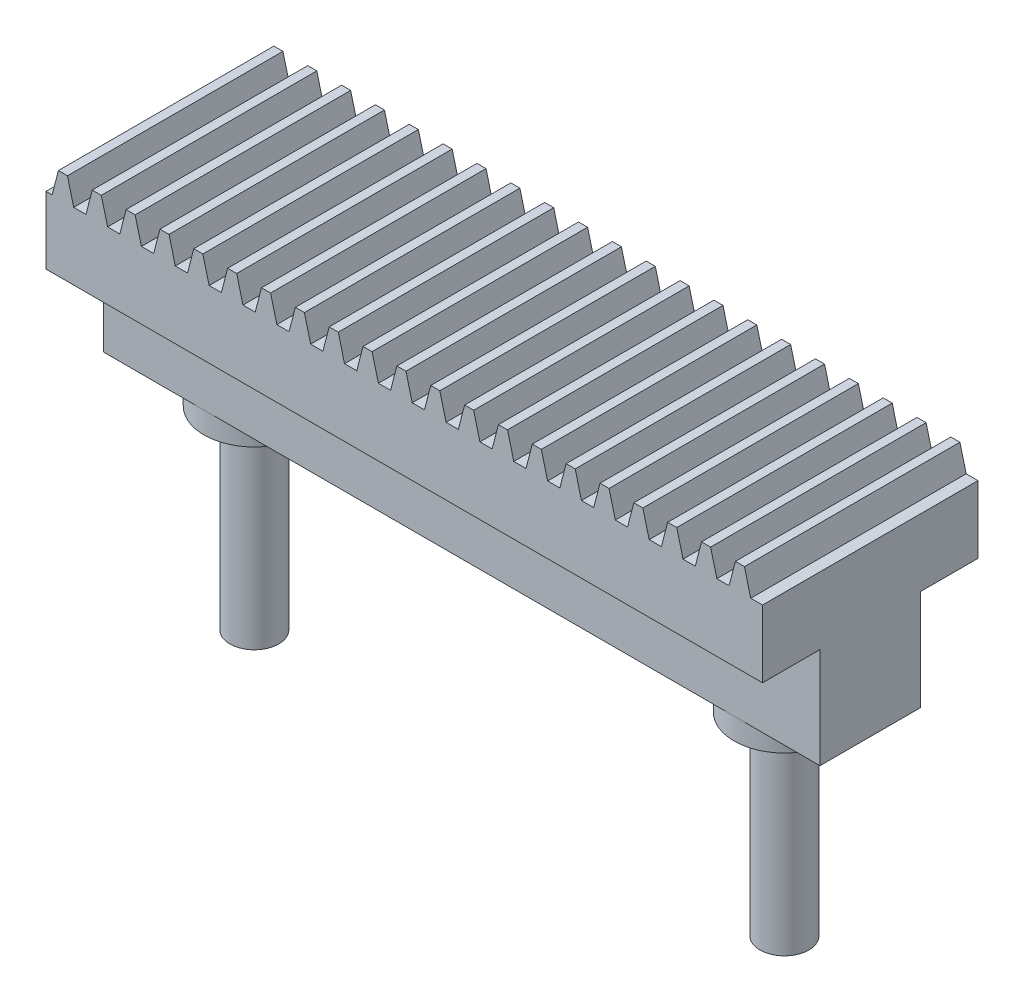
SolidWorks part; units mm, degrees
extrude "Blank" add sketch "BlankSke" against normal blind 20
sketch "BlankSke" plane through (0, 0, 0) normal (0, 0, 1) x (1, 0, 0)
  line L1 (0, 0) -> (100, 0)
  line L2 (0, 0) -> (0, 12.75)
  line L3 (0, 12.75) -> (100, 12.75)
  line L4 (100, 0) -> (100, 12.75)
  dimension "Length" = 100
ref_plane "Plane1" through (0, 0, 0) normal (0, 0, 1) x (1, 0, 0)
ref_plane "Plane2" through (0, 0, 0) normal (0, 1, 0) x (1, 0, 0)
ref_plane "Plane3" through (0, 0, 0) normal (1, 0, 0) x (0, 0, -1)
other "Configuration Table"
sketch "HoldingSke" plane through (0, 0, 0) normal (0, 1, 0) x (1, 0, 0)
  line L0 (0, 0) -> (0.0928, 0.6602)
  line L1 (-15, 0) -> (100, 0) construction
  line L2 (0, 0) -> (-2.1039, 2.3779)
  line L3 (0, 0) -> (-11.863, 4.5341)
  line L4 (0, 0) -> (7.9495, 3.3743)
  line L5 (0, 0) -> (-23.7986, -8.8762)
  line L6 (0, 0) -> (-10.5278, -7.1032)
  line L9 (-67.7845, 28.3722) -> (29.0302, 53.4102)
  line L10 (-76.2, 3.8779) -> (-64.95, 3.8779)
  line L11 (0, 0) -> (-20, 0)
  line L12 (-76.2, 101.6) -> (-76.147, 101.6)
  line L13 (24.9733, 27.94) -> (52.9518, 28.4284)
  line L14 (24.9733, 27.94) -> (24.9743, 27.94)
  line L15 (24.9733, 27.94) -> (100.4006, 29.5858)
  circle A0 centre (0, 0) radius 19.05
  circle A1 centre (0, 0) radius 5.625
  circle A2 centre (0, 0) radius 12.7
  dimension "Num_teeth" = 23
  dimension "Width" = 20
  dimension "Length" = 100
  dimension "Pitch_height" = 11.25
sketch "TooCutSkeIll" plane through (0, 0, 0) normal (0, 0, 1) x (1, 0, 0)
  line L0 (-1.7134, 12.705) -> (-0.9251, 9.6569)
  line L1 (-0.5611, 9.375) -> (0.5611, 9.375)
  line L2 (0.9251, 9.6569) -> (1.7134, 12.705)
  line L3 (100, 12.75) -> (0, 12.75) construction
  line L4 (0, 0) -> (0, 64.897) construction
  line L5 (-13.208, 11.25) -> (12.954, 11.25) construction
  line L6 (0, 0) -> (100, 0) construction
  line L7 (1.3371, 11.25) -> (1.3371, 48.7463) construction
  line L8 (-1.3371, 11.25) -> (-1.3371, 48.7463) construction
  line L9 (1.7715, 12.75) -> (1.7715, 12.7754)
  line L10 (-1.7715, 12.75) -> (-1.7715, 12.7754)
  line L11 (-1.7715, 12.7754) -> (1.7715, 12.7754)
  arc A0 (0.5611, 9.375) -> (0.9251, 9.6569) centre (0.5611, 9.751) ccw
  arc A1 (-0.9251, 9.6569) -> (-0.5611, 9.375) centre (-0.5611, 9.751) ccw
  arc A2 (1.7715, 12.75) -> (1.7134, 12.705) centre (1.7715, 12.69) ccw
  arc A3 (-1.7134, 12.705) -> (-1.7715, 12.75) centre (-1.7715, 12.69) ccw
  dimension "Addendum_plus" = 1.5254
  dimension "Pitch_height" = 11.25
  dimension "Pressure_angle" = 14.5
  dimension "Gap_width" = 2.6742
  dimension "Dedendum" = 1.875
extrude "ToothCutIll" [suppressed] cut sketch "TooCutSkeIll" against normal through all
sketch "TooCutSkeSim" plane through (0, 0, 0) normal (0, 0, 1) x (1, 0, 0)
  line L0 (0.8522, 9.375) -> (-0.8522, 9.375)
  line L1 (1.7316, 12.7754) -> (0.8522, 9.375)
  line L2 (0, 17.4625) -> (0, 53.467) construction
  line L3 (1.7316, 12.7754) -> (-1.7316, 12.7754)
  line L6 (-1.7316, 12.7754) -> (-0.8522, 9.375)
  line L9 (-1.3371, 11.25) -> (1.3371, 11.25) construction
  line L10 (0, 0) -> (100, 0) construction
  line L11 (1.3371, 11.25) -> (1.3371, 53.467) construction
  line L12 (-1.3371, 11.25) -> (-1.3371, 53.467) construction
  dimension "Addendum_plus" = 1.5254
  dimension "Pitch_height" = 11.25
  dimension "Pressure_angle" = 14.5
  dimension "Gap_width" = 2.6742
  dimension "Dedendum" = 1.875
extrude "ToothCutSim" cut sketch "TooCutSkeSim" against normal through all
pattern_linear "TeethCuts" count 23 spacing 4.7124 along (1, 0, 0) of "ToothCutIll", "ToothCutSim"
sketch "Croquis1" plane through (0, 0, 0) normal (0, 0, 1) x (1, 0, 0)
  line L89 (99.8124, 9.375) -> (98.108, 9.375)
  line L90 (98.108, 9.375) -> (97.2351, 12.75)
  line L91 (97.2351, 12.75) -> (95.9728, 12.75)
  line L92 (95.9728, 12.75) -> (95.1, 9.375)
  line L93 (95.1, 9.375) -> (93.3956, 9.375)
  line L94 (93.3956, 9.375) -> (92.5228, 12.75)
  line L95 (92.5228, 12.75) -> (91.2604, 12.75)
  line L96 (91.2604, 12.75) -> (90.3876, 9.375)
  line L97 (90.3876, 9.375) -> (88.6832, 9.375)
  line L98 (88.6832, 9.375) -> (87.8104, 12.75)
  line L99 (87.8104, 12.75) -> (86.548, 12.75)
  line L100 (86.548, 12.75) -> (85.6752, 9.375)
  line L101 (85.6752, 9.375) -> (83.9708, 9.375)
  line L102 (83.9708, 9.375) -> (83.098, 12.75)
  line L103 (83.098, 12.75) -> (81.8356, 12.75)
  line L104 (81.8356, 12.75) -> (80.9628, 9.375)
  line L105 (80.9628, 9.375) -> (79.2584, 9.375)
  line L106 (79.2584, 9.375) -> (78.3856, 12.75)
  line L107 (78.3856, 12.75) -> (77.1232, 12.75)
  line L108 (77.1232, 12.75) -> (76.2504, 9.375)
  line L109 (76.2504, 9.375) -> (74.546, 9.375)
  line L110 (74.546, 9.375) -> (73.6732, 12.75)
  line L111 (73.6732, 12.75) -> (72.4109, 12.75)
  line L112 (72.4109, 12.75) -> (71.538, 9.375)
  line L113 (71.538, 9.375) -> (69.8336, 9.375)
  line L114 (69.8336, 9.375) -> (68.9608, 12.75)
  line L115 (68.9608, 12.75) -> (67.6985, 12.75)
  line L116 (67.6985, 12.75) -> (66.8256, 9.375)
  line L117 (66.8256, 9.375) -> (65.1213, 9.375)
  line L118 (65.1213, 9.375) -> (64.2484, 12.75)
  line L119 (64.2484, 12.75) -> (62.9861, 12.75)
  line L120 (62.9861, 12.75) -> (62.1132, 9.375)
  line L121 (62.1132, 9.375) -> (60.4089, 9.375)
  line L122 (60.4089, 9.375) -> (59.536, 12.75)
  line L123 (59.536, 12.75) -> (58.2737, 12.75)
  line L124 (58.2737, 12.75) -> (57.4009, 9.375)
  line L125 (57.4009, 9.375) -> (55.6965, 9.375)
  line L126 (55.6965, 9.375) -> (54.8236, 12.75)
  line L127 (54.8236, 12.75) -> (53.5613, 12.75)
  line L128 (53.5613, 12.75) -> (52.6885, 9.375)
  line L129 (52.6885, 9.375) -> (50.9841, 9.375)
  line L130 (50.9841, 9.375) -> (50.1113, 12.75)
  line L131 (50.1113, 12.75) -> (48.8489, 12.75)
  line L132 (48.8489, 12.75) -> (47.9761, 9.375)
  line L133 (47.9761, 9.375) -> (46.2717, 9.375)
  line L134 (46.2717, 9.375) -> (45.3989, 12.75)
  line L135 (45.3989, 12.75) -> (44.1365, 12.75)
  line L136 (44.1365, 12.75) -> (43.2637, 9.375)
  line L137 (43.2637, 9.375) -> (41.5593, 9.375)
  line L138 (41.5593, 9.375) -> (40.6865, 12.75)
  line L139 (40.6865, 12.75) -> (39.4241, 12.75)
  line L140 (39.4241, 12.75) -> (38.5513, 9.375)
  line L141 (38.5513, 9.375) -> (36.8469, 9.375)
  line L142 (36.8469, 9.375) -> (35.9741, 12.75)
  line L143 (35.9741, 12.75) -> (34.7117, 12.75)
  line L144 (34.7117, 12.75) -> (33.8389, 9.375)
  line L145 (33.8389, 9.375) -> (32.1345, 9.375)
  line L146 (32.1345, 9.375) -> (31.2617, 12.75)
  line L147 (31.2617, 12.75) -> (29.9994, 12.75)
  line L148 (29.9994, 12.75) -> (29.1265, 9.375)
  line L149 (29.1265, 9.375) -> (27.4221, 9.375)
  line L150 (27.4221, 9.375) -> (26.5493, 12.75)
  line L151 (26.5493, 12.75) -> (25.287, 12.75)
  line L152 (25.287, 12.75) -> (24.4141, 9.375)
  line L153 (24.4141, 9.375) -> (22.7098, 9.375)
  line L154 (22.7098, 9.375) -> (21.8369, 12.75)
  line L155 (21.8369, 12.75) -> (20.5746, 12.75)
  line L156 (20.5746, 12.75) -> (19.7017, 9.375)
  line L157 (19.7017, 9.375) -> (17.9974, 9.375)
  line L158 (17.9974, 9.375) -> (17.1245, 12.75)
  line L159 (17.1245, 12.75) -> (15.8622, 12.75)
  line L160 (15.8622, 12.75) -> (14.9894, 9.375)
  line L161 (14.9894, 9.375) -> (13.285, 9.375)
  line L162 (13.285, 9.375) -> (12.4121, 12.75)
  line L163 (12.4121, 12.75) -> (11.1498, 12.75)
  line L164 (11.1498, 12.75) -> (10.277, 9.375)
  line L165 (10.277, 9.375) -> (8.5726, 9.375)
  line L166 (8.5726, 9.375) -> (7.6998, 12.75)
  line L167 (7.6998, 12.75) -> (6.4374, 12.75)
  line L168 (6.4374, 12.75) -> (5.5646, 9.375)
  line L169 (5.5646, 9.375) -> (3.8602, 9.375)
  line L170 (3.8602, 9.375) -> (2.9874, 12.75)
  line L171 (2.9874, 12.75) -> (1.725, 12.75)
  line L172 (1.725, 12.75) -> (0.8522, 9.375)
  line L173 (0.8522, 9.375) -> (0, 9.375)
  line L174 (0, 9.375) -> (0, 0)
  line L175 (0, 0) -> (100, 0)
  line L176 (100, 0) -> (100, 10.1006)
  line L177 (100, 10.1006) -> (99.8124, 9.375)
  line L178 (99.8124, 9.375) -> (98.108, 9.375)
  line L179 (98.108, 9.375) -> (97.2351, 12.75)
  line L180 (97.2351, 12.75) -> (95.9728, 12.75)
  line L181 (95.9728, 12.75) -> (95.1, 9.375)
  line L182 (95.1, 9.375) -> (93.3956, 9.375)
  line L183 (93.3956, 9.375) -> (92.5228, 12.75)
  line L184 (92.5228, 12.75) -> (91.2604, 12.75)
  line L185 (91.2604, 12.75) -> (90.3876, 9.375)
  line L186 (90.3876, 9.375) -> (88.6832, 9.375)
  line L187 (88.6832, 9.375) -> (87.8104, 12.75)
  line L188 (87.8104, 12.75) -> (86.548, 12.75)
  line L189 (86.548, 12.75) -> (85.6752, 9.375)
  line L190 (85.6752, 9.375) -> (83.9708, 9.375)
  line L191 (83.9708, 9.375) -> (83.098, 12.75)
  line L192 (83.098, 12.75) -> (81.8356, 12.75)
  line L193 (81.8356, 12.75) -> (80.9628, 9.375)
  line L194 (80.9628, 9.375) -> (79.2584, 9.375)
  line L195 (79.2584, 9.375) -> (78.3856, 12.75)
  line L196 (78.3856, 12.75) -> (77.1232, 12.75)
  line L197 (77.1232, 12.75) -> (76.2504, 9.375)
  line L198 (76.2504, 9.375) -> (74.546, 9.375)
  line L199 (74.546, 9.375) -> (73.6732, 12.75)
  line L200 (73.6732, 12.75) -> (72.4109, 12.75)
  line L201 (72.4109, 12.75) -> (71.538, 9.375)
  line L202 (71.538, 9.375) -> (69.8336, 9.375)
  line L203 (69.8336, 9.375) -> (68.9608, 12.75)
  line L204 (68.9608, 12.75) -> (67.6985, 12.75)
  line L205 (67.6985, 12.75) -> (66.8256, 9.375)
  line L206 (66.8256, 9.375) -> (65.1213, 9.375)
  line L207 (65.1213, 9.375) -> (64.2484, 12.75)
  line L208 (64.2484, 12.75) -> (62.9861, 12.75)
  line L209 (62.9861, 12.75) -> (62.1132, 9.375)
  line L210 (62.1132, 9.375) -> (60.4089, 9.375)
  line L211 (60.4089, 9.375) -> (59.536, 12.75)
  line L212 (59.536, 12.75) -> (58.2737, 12.75)
  line L213 (58.2737, 12.75) -> (57.4009, 9.375)
  line L214 (57.4009, 9.375) -> (55.6965, 9.375)
  line L215 (55.6965, 9.375) -> (54.8236, 12.75)
  line L216 (54.8236, 12.75) -> (53.5613, 12.75)
  line L217 (53.5613, 12.75) -> (52.6885, 9.375)
  line L218 (52.6885, 9.375) -> (50.9841, 9.375)
  line L219 (50.9841, 9.375) -> (50.1113, 12.75)
  line L220 (50.1113, 12.75) -> (48.8489, 12.75)
  line L221 (48.8489, 12.75) -> (47.9761, 9.375)
  line L222 (47.9761, 9.375) -> (46.2717, 9.375)
  line L223 (46.2717, 9.375) -> (45.3989, 12.75)
  line L224 (45.3989, 12.75) -> (44.1365, 12.75)
  line L225 (44.1365, 12.75) -> (43.2637, 9.375)
  line L226 (43.2637, 9.375) -> (41.5593, 9.375)
  line L227 (41.5593, 9.375) -> (40.6865, 12.75)
  line L228 (40.6865, 12.75) -> (39.4241, 12.75)
  line L229 (39.4241, 12.75) -> (38.5513, 9.375)
  line L230 (38.5513, 9.375) -> (36.8469, 9.375)
  line L231 (36.8469, 9.375) -> (35.9741, 12.75)
  line L232 (35.9741, 12.75) -> (34.7117, 12.75)
  line L233 (34.7117, 12.75) -> (33.8389, 9.375)
  line L234 (33.8389, 9.375) -> (32.1345, 9.375)
  line L235 (32.1345, 9.375) -> (31.2617, 12.75)
  line L236 (31.2617, 12.75) -> (29.9994, 12.75)
  line L237 (29.9994, 12.75) -> (29.1265, 9.375)
  line L238 (29.1265, 9.375) -> (27.4221, 9.375)
  line L239 (27.4221, 9.375) -> (26.5493, 12.75)
  line L240 (26.5493, 12.75) -> (25.287, 12.75)
  line L241 (25.287, 12.75) -> (24.4141, 9.375)
  line L242 (24.4141, 9.375) -> (22.7098, 9.375)
  line L243 (22.7098, 9.375) -> (21.8369, 12.75)
  line L244 (21.8369, 12.75) -> (20.5746, 12.75)
  line L245 (20.5746, 12.75) -> (19.7017, 9.375)
  line L246 (19.7017, 9.375) -> (17.9974, 9.375)
  line L247 (17.9974, 9.375) -> (17.1245, 12.75)
  line L248 (17.1245, 12.75) -> (15.8622, 12.75)
  line L249 (15.8622, 12.75) -> (14.9894, 9.375)
  line L250 (14.9894, 9.375) -> (13.285, 9.375)
  line L251 (13.285, 9.375) -> (12.4121, 12.75)
  line L252 (12.4121, 12.75) -> (11.1498, 12.75)
  line L253 (11.1498, 12.75) -> (10.277, 9.375)
  line L254 (10.277, 9.375) -> (8.5726, 9.375)
  line L255 (8.5726, 9.375) -> (7.6998, 12.75)
  line L256 (7.6998, 12.75) -> (6.4374, 12.75)
  line L257 (6.4374, 12.75) -> (5.5646, 9.375)
  line L258 (5.5646, 9.375) -> (3.8602, 9.375)
  line L259 (3.8602, 9.375) -> (2.9874, 12.75)
  line L260 (2.9874, 12.75) -> (1.725, 12.75)
  line L261 (1.725, 12.75) -> (0.8522, 9.375)
  line L262 (0.8522, 9.375) -> (0, 9.375)
  line L263 (0, 9.375) -> (0, 0)
  line L264 (0, 0) -> (100, 0)
  line L265 (100, 0) -> (100, 10.1006)
  line L266 (100, 10.1006) -> (99.8124, 9.375)
  dimension "D1" = 0
extrude "Saliente-Extruir1" add sketch "Croquis1" along normal blind 10
sketch "Croquis12" plane through (100, 0, 0) normal (1, 0, 0) x (0, 0, -1)
  line L4 (20, 10.1006) -> (-10, 10.1006)
  line L5 (-10, 10.1006) -> (-10, 0)
  line L6 (-10, 0) -> (20, 0)
  line L7 (20, 0) -> (20, 10.1006)
  line L8 (20, 10.1006) -> (-10, 10.1006)
  line L9 (-10, 10.1006) -> (-10, 0)
  line L10 (-10, 0) -> (20, 0)
  line L11 (20, 0) -> (20, 10.1006)
  dimension "D1" = 0
extrude "Cortar-Extruir1" cut sketch "Croquis12" against normal blind 0.25 and the other way through all
ref_plane "Plano1" through (0, 0, -5) normal (0, 0, 1) x (1, 0, 0)
sketch "Croquis13" plane through (0, 0, 0) normal (0, -1, 0) x (1, 0, 0)
  line L0 (0, -5) -> (107.4582, -5) construction
  line L1 (0, 2) -> (99.75, 2)
  line L2 (99.75, 10) -> (99.75, -20) construction
  line L3 (99.75, 2) -> (99.75, -12)
  line L4 (0, -20) -> (99.75, -20)
  line L5 (99.75, -20) -> (99.75, 10)
  line L6 (99.75, 10) -> (0, 10)
  line L7 (0, 10) -> (0, -20)
  line L11 (0, 10) -> (0, -20) construction
  line L12 (0, 2) -> (0, -12)
  line L13 (0, -12) -> (99.75, -12)
  point P11 (99.75, -5)
  dimension "D2" = 7
  dimension "D1" = 0
extrude "Saliente-Extruir6" add sketch "Croquis13" along normal blind 14
sketch "Croquis14" plane through (0, -14, 0) normal (0, -1, 0) x (1, 0, 0)
  line L0 (0, -5) -> (108.0787, -5) construction
  line L4 (0, 2) -> (0, -12)
  line L5 (0, -12) -> (99.75, -12)
  line L6 (99.75, -12) -> (99.75, 2)
  line L7 (99.75, 2) -> (0, 2)
  line L8 (0, 2) -> (0, -12) construction
  line L9 (0, -12) -> (99.75, -12) construction
  line L10 (99.75, -12) -> (99.75, 2) construction
  line L11 (99.75, 2) -> (0, 2) construction
  circle A0 centre (14, -5) radius 3.4
  circle A1 centre (87.8, -5) radius 3.4
  circle A2 centre (14, -5) radius 7
  circle A3 centre (87.8, -5) radius 7
  dimension "D2" = 6.8
  dimension "D3" = 73.8
  dimension "D4" = 14
  dimension "D1" = 0
extrude "Saliente-Extruir7" add sketch "Croquis14" along normal blind 3
sketch "Croquis15" plane through (0, -14, 0) normal (0, -1, 0) x (1, 0, 0)
  circle A0 centre (87.8, -5) radius 3.4 construction
  circle A1 centre (14, -5) radius 3.4 construction
  circle A2 centre (87.8, -5) radius 3.4
  circle A3 centre (14, -5) radius 3.4
extrude "Saliente-Extruir8" add sketch "Croquis15" along normal blind 30
equation "' \"Module@HoldingSke\" = 6.35"
equation "' \"Num_teeth@HoldingSke\" = 12"
equation "' \"Ap@HoldingSke\" =  20"
equation "' \"Ap@HoldingSke\" = 20"
equation "' \"Width@HoldingSke\" = 0.25 * 25.4"
equation "' \"Show_teeth@HoldingSke\" = 500"
equation "' \"Backlash@HoldingSke\" = 0.009 * 25.4"
equation "' \"Addendum_fac@HoldingSke\" = 1.0"
equation "' \"Dedendum_fac@HoldingSke\" = 1.25"
equation "' \"Dedendum_add@HoldingSke\" = 0.00005 * 25.4"
equation "' \"Clearance_fac@HoldingSke\" = 0.25"
equation "' \"Pitch_height@HoldingSke\" = 1 * 25.4"
equation "' \"Length@HoldingSke\" = 4.71 * 25.4"
equation "\"Pitch@HoldingSke\" = 1 / \"Module@HoldingSke\""
equation "\"MPH@HoldingSke\" = \"Dedendum_fac@HoldingSke\" / \"Pitch@HoldingSke\" + 2 * \"Dedendum_add@HoldingSke\" + 0.002 * 25.4"
equation "\"MPH@HoldingSke\" = ((sgn( \"MPH@HoldingSke\" - \"Pitch_height@HoldingSke\")+1)*( \"MPH@HoldingSke\" - \"Pitch_height@HoldingSke\"))/2 + \"Pitch_height@HoldingSke\""
equation "\"Blank_height@BlankSke\" = \"Pitch_height@HoldingSke\" + \"Addendum_fac@HoldingSke\"  / \"Pitch@HoldingSke\" "
equation "\"Length@BlankSke\" =  \"Length@HoldingSke\""
equation "\"Face_width@Blank\" = \"Width@HoldingSke\""
equation "\"Pressure_angle@TooCutSkeIll\" = \"Ap@HoldingSke\""
equation "\"Addendum_plus@TooCutSkeIll\" =  \"Addendum_fac@HoldingSke\"  / \"Pitch@HoldingSke\" + 0.001 *25.4"
equation "\"Dedendum@TooCutSkeIll\" = \"Dedendum_fac@HoldingSke\"  / \"Pitch@HoldingSke\""
equation "\"Pitch_height@TooCutSkeIll\" =  \"MPH@HoldingSke\""
equation "\"Gap_width@TooCutSkeIll\" = 3.14159265 / 2 / \"Pitch@HoldingSke\" + 6 * \"Backlash@HoldingSke\""
equation "\"Pressure_angle@TooCutSkeSim\" = \"Ap@HoldingSke\""
equation "\"Addendum_plus@TooCutSkeSim\" =  \"Addendum_fac@HoldingSke\"  / \"Pitch@HoldingSke\" + 0.001 * 25.4"
equation "\"Dedendum@TooCutSkeSim\" = \"Dedendum_fac@HoldingSke\"  / \"Pitch@HoldingSke\""
equation "\"Pitch_height@TooCutSkeSim\" =  \"MPH@HoldingSke\""
equation "\"Gap_width@TooCutSkeSim\" = 3.14159265 / 2 / \"Pitch@HoldingSke\" + 6 * \"Backlash@HoldingSke\""
equation "\"Root_fillet@TooCutSkeIll\" = \"Clearance_fac@HoldingSke\" / \"Pitch@HoldingSke\" + \"Dedendum_add@HoldingSke\""
equation "\"Break_rad@TooCutSkeIll\" = 0.02 / \"Pitch@HoldingSke\" * 2"
equation "\"Linear_pitch@TeethCuts\" = 3.14159265 / \"Pitch@HoldingSke\""
equation "\"Num_teeth@HoldingSke\" = int( ( \"Length@HoldingSke\" + 0 ) / (3.14159265 / \"Pitch@HoldingSke\")) + 0.9999  + 1"
equation " \"Num_teeth@TeethCuts\" = int( \"Show_teeth@HoldingSke\" ) + 1"
equation " \"Num_teeth@TeethCuts\" = ((sgn( \"Num_teeth@TeethCuts\" - \"Num_teeth@HoldingSke\" )-1)*( \"Num_teeth@TeethCuts\" - \"Num_teeth@HoldingSke\" ))/-2+ \"Num_teeth@HoldingSke\""
equation " \"Num_teeth@TeethCuts\" = ((sgn( \"Num_teeth@TeethCuts\" - 2.0)+1)*( \"Num_teeth@TeethCuts\" - 2.0))/2 +2.0"
